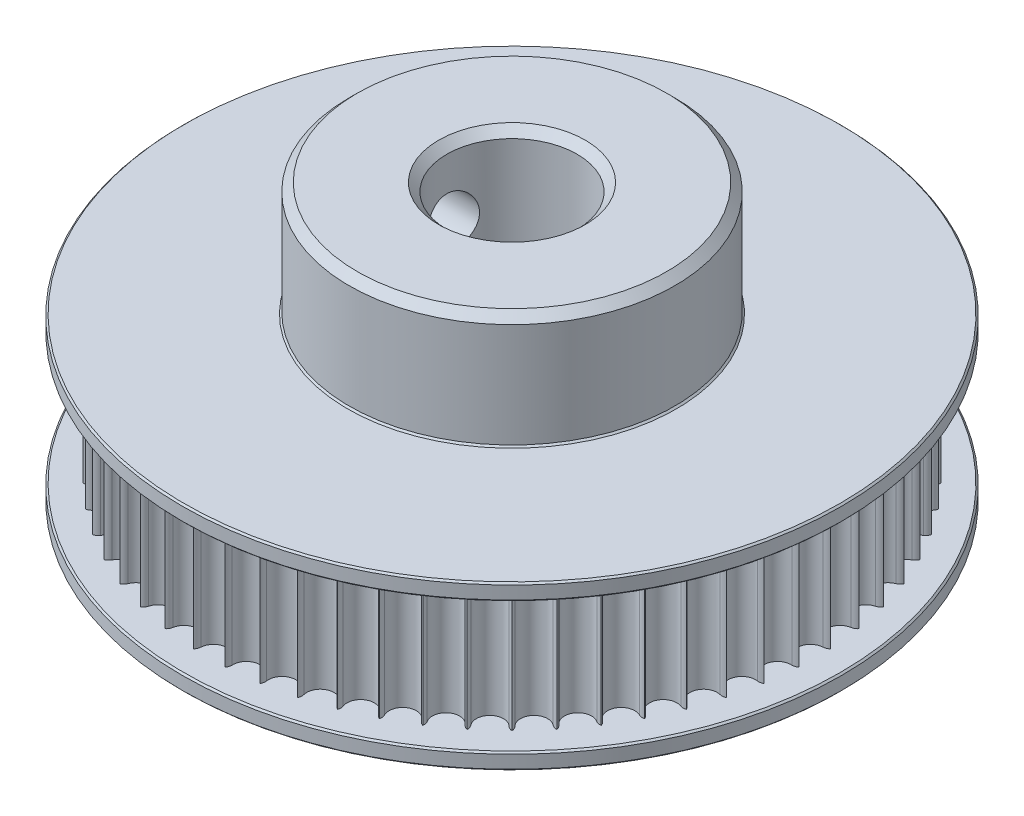
SolidWorks part; units mm, degrees
ref_plane "Front plan" through (0, 0, 0) normal (0, 0, 1) x (1, 0, 0)
ref_plane "Top plan" through (0, 0, 0) normal (0, 1, 0) x (1, 0, 0)
ref_plane "Right plan" through (0, 0, 0) normal (1, 0, 0) x (0, 0, -1)
sketch "Skica2" plane through (0, 0, 0) normal (0, 0, 1) x (1, 0, 0)
  line L0 (10, 9) -> (4, 9)
  line L1 (4, 9) -> (4, -9)
  line L2 (4, -9) -> (5, -9)
  line L3 (0, -9) -> (0, 9) construction
  line L4 (0, 9) -> (4, 9)
  line L5 (0, -9) -> (4, -9)
  line L6 (5, -9) -> (5, -8)
  line L7 (20.25, 1) -> (18.8, 1)
  line L8 (18.8, 1) -> (18.8, -7)
  line L9 (20.25, 1) -> (20.25, 2)
  line L12 (20.25, -8) -> (5, -8)
  line L13 (20.25, 2) -> (10, 2)
  line L14 (20.25, -8) -> (20.25, -7)
  line L15 (18.8, -7) -> (20.25, -7)
  line L16 (10, 2) -> (10, 9)
  point P6 (12.625, -8)
  point P7 (0, 0)
  dimension "D2" = 1
  dimension "D6" = 40.5
  dimension "D3" = 37.6
  dimension "D1" = 8
  dimension "D8" = 18
  dimension "D4" = 1
  dimension "D7" = 20
  dimension "D9" = 7
  dimension "D5" = 1
revolve "Revolute" add sketch "Skica2" angle 360 about L3 region at (10.5329, -1.1872, 0)
sketch "Sketch2" plane through (0, 1, 0) normal (0, -1, 0) x (1, 0, 0)
  line L0 (0, 0) -> (0, 18.3305) construction
  line L1 (0, 0) -> (6.3393, 17.699) construction
  line L3 (0, 0) -> (-2.1448, 18.6773) construction
  circle A1 centre (0, 0) radius 17.4945 construction
  circle A2 centre (0, 0) radius 18.3 construction
  arc A3 (-0.8345, 18.281) -> (0.8345, 18.281) centre (0, 18.3305) ccw
  arc A7 (-1.3701, 18.75) -> (-2.1448, 18.6773) centre (0, 0) ccw
  arc A8 (0, 20.2554) -> (2.1448, 18.6773) centre (0.5756, 18.7912) cw
  circle A9 centre (0, 0) radius 18.8 construction
  arc A10 (1.3701, 18.75) -> (2.1448, 18.6773) centre (0, 0) cw
  arc A11 (1.3701, 18.75) -> (0.8345, 18.281) centre (1.3336, 18.2513) ccw
  arc A12 (0, 20.2554) -> (-2.1448, 18.6773) centre (-0.5756, 18.7912) ccw
  arc A13 (-1.3701, 18.75) -> (-0.8345, 18.281) centre (-1.3336, 18.2513) cw
  dimension "D2" = 1
  dimension "D4" = 0.836
  dimension "D6" = 37.6
  dimension "D3" = 1.5733
  dimension "D1" = 0.5
extrude "Cut-Extrude3" cut sketch "Sketch2" along normal up to surface (8 mm away) up to face at (20.25, -7, 0)
pattern_circular "CirPattern1" count 60 over 360 about axis through (0, -9, 0) along (0, -1, 0) of "Cut-Extrude3"
sketch "Sketch3" plane through (0, 0, 0) normal (1, 0, 0) x (0, 0, -1)
  line L0 (0, 9) -> (0, 0.5) construction
  line L1 (4, 9) -> (-4, 9) construction
  circle A0 centre (0, 4.75) radius 1.65
  dimension "D1" = 3.3
extrude "Cut-Extrude2" cut sketch "Sketch3" against normal up to next
chamfer "Chamfer1" distance 1 angle 45 1 edges at (5, -8, 0)
chamfer "Chamfer2" distance 0.5 angle 45 2 edges at (10, 9, 0) (4, 9, 0)
chamfer "Chamfer3" distance 0.1 angle 45 5 edges at (20.25, -8, 0) (20.25, -7, 0) (20.25, 1, 0) (20.25, 2, 0) (10, 2, 0)
equation "\"`\"=2"
equation "\"D6@Sketch2\"= \"D3@Skica2\""
